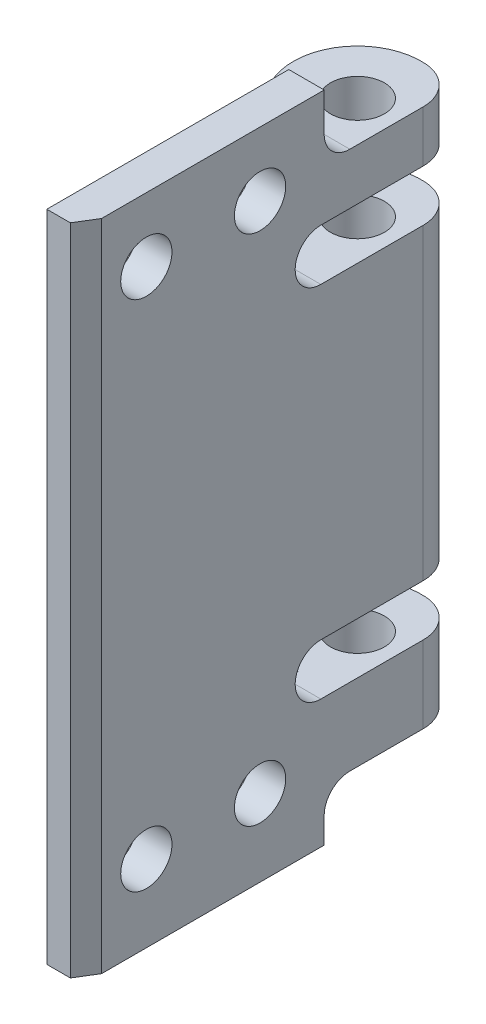
SolidWorks part; units mm, degrees
ref_plane "Front Plane" through (0, 0, 0) normal (0, 0, 1) x (1, 0, 0)
ref_plane "Top Plane" through (0, 0, 0) normal (0, 1, 0) x (1, 0, 0)
ref_plane "Right Plane" through (0, 0, 0) normal (1, 0, 0) x (0, 0, -1)
sketch "Sketch1" plane through (0, 0, 0) normal (0, 1, 0) x (1, 0, 0)
  line L0 (143.3333, 493) -> (716.6667, 493) construction
  line L1 (57.1966, 9.0284) -> (57.1966, 28.64)
  line L4 (59.9567, 29.7327) -> (59.9567, 10.5387)
  line L5 (59.9567, 10.5387) -> (59.0306, 9.0284)
  line L6 (59.0306, 9.0284) -> (57.1966, 9.0284)
  line L7 (59.9567, 29.7327) -> (59.9567, 37.5187)
  line L8 (64.209, 27.9079) -> (65.0991, 27.0179)
  line L13 (64.654, 7.1943) -> (64.654, 5.5805)
  line L16 (63.4817, 13.8234) -> (63.1068, 13.4485)
  arc A1 (59.9567, 37.5187) -> (57.1966, 28.64) centre (56.819, 33.6257) ccw
  circle A4 centre (56.819, 33.6257) radius 2.1
extrude "Boss-Extrude1" add sketch "Sketch1" along normal blind 51 contours L13 L8 L4 L16 | L1 L6 L5 L4 A4 region at (57.3358, 0, -26.3948)
sketch "Sketch2" plane through (59.9567, 0, 0) normal (1, 0, 0) x (0, 0, -1)
  line L0 (0, 0) -> (0, 10) construction
  line L2 (39.1338, 10) -> (25.6338, 10)
  line L11 (39.1338, 14) -> (39.1338, 10)
  line L14 (39.1338, 14) -> (27.8951, 14)
  line L15 (25.6338, 10) -> (25.6338, 14)
  line L18 (25.6338, 14) -> (27.8951, 14)
extrude "Cut-Extrude1" cut sketch "Sketch2" against normal mid plane 30
sketch "Sketch3" plane through (59.9567, 0, 0) normal (1, 0, 0) x (0, 0, -1)
  line L0 (9.0284, 51) -> (9.0284, 40) construction
  line L1 (9.0284, 51) -> (9.0284, 0) construction
  line L3 (25.6338, 14) -> (25.6338, 47.1784) construction
  line L12 (41.7113, 42) -> (27.8951, 42)
  line L14 (41.7113, 42) -> (41.7113, 38)
  line L18 (41.7113, 38) -> (25.6338, 38)
  line L20 (25.6338, 38) -> (25.6338, 42)
  line L21 (25.6338, 42) -> (27.8951, 42)
extrude "Cut-Extrude2" cut sketch "Sketch3" against normal mid plane 25
sketch "Sketch4" plane through (59.9567, 0, 0) normal (1, 0, 0) x (0, 0, -1)
  line L1 (38.8451, 0) -> (38.8451, 4)
  line L4 (38.8451, 51) -> (30.0565, 51)
  line L6 (38.8451, 4) -> (27.8951, 4)
  line L13 (27.8951, 4) -> (27.8951, 0)
  line L17 (38.8451, 0) -> (27.8951, 0)
  line L20 (27.8951, 47) -> (27.8951, 51)
  line L21 (27.8951, 51) -> (30.0565, 51)
  line L23 (38.8451, 51) -> (38.8451, 46)
  line L24 (38.8451, 46) -> (27.8951, 46)
  line L25 (27.8951, 46) -> (27.8951, 47)
extrude "Cut-Extrude3" cut sketch "Sketch4" against normal mid plane 50
sketch "Sketch5" plane through (57.1966, 0, 0) normal (-1, 0, 0) x (0, 0, 1)
  line L0 (-27.8951, 51) -> (-22.8951, 51) construction
  line L1 (-9.0284, 51) -> (-27.8951, 51) construction
  line L2 (-22.8951, 51) -> (-22.8951, 46) construction
  line L3 (-18.4617, 51) -> (-18.4617, 40.0063) construction
  line L4 (-27.8951, 26) -> (-14.7419, 26) construction
  circle A0 centre (-22.8951, 46) radius 2
  circle A1 centre (-14.0284, 46) radius 2
  circle A2 centre (-14.0284, 6) radius 2
  circle A3 centre (-22.8951, 6) radius 2
extrude "Cut-Extrude4" cut sketch "Sketch5" against normal blind 10
fillet "Fillet4" radius 2 1 edges at (57.1966, 26, -28.64)
fillet "Fillet5" radius 3 3 edges at (59.9567, 7, -37.5187) (59.9567, 26, -37.5187) (59.9567, 44, -37.5187)
fillet "Fillet6" radius 2 6 edges at (58.5767, 4, -27.8951) (58.5767, 46, -27.8951) (58.5767, 10, -25.6338) (58.5767, 14, -25.6338) (58.5767, 42, -25.6338) (58.5767, 38, -25.6338)
